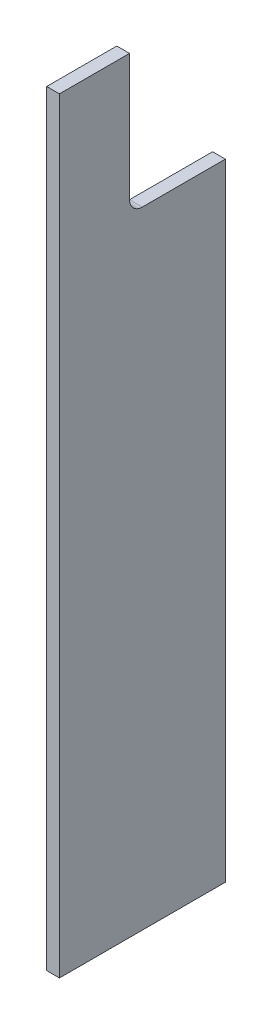
SolidWorks part; units mm, degrees
ref_plane "Plan de face" through (0, 0, 0) normal (0, 0, 1) x (1, 0, 0)
ref_plane "Plan de dessus" through (0, 0, 0) normal (0, 1, 0) x (1, 0, 0)
ref_plane "Plan de droite" through (0, 0, 0) normal (1, 0, 0) x (0, 0, -1)
sketch "Esquisse1" plane through (0, 0, 0) normal (0, 0, 1) x (1, 0, 0)
  line L0 (-91.2495, 0) -> (-222.1354, 0) construction
  line L1 (-155.642, 600) -> (-165.642, 600)
  line L2 (-155.642, 600) -> (-155.642, 0)
  line L3 (-155.642, 0) -> (-165.642, 0)
  line L4 (-165.642, 600) -> (-165.642, 0)
  dimension "D1" = 10
extrude "Boss.-Extru.1" add sketch "Esquisse1" along normal up to surface (129.974 mm away)
sketch "Esquisse2" plane through (-155.642, 0, 0) normal (1, 0, 0) x (0, 0, -1)
  line L0 (0, 0) -> (0, 600) construction
  line L1 (0, 600) -> (-75.046, 600)
  line L2 (0, 600) -> (0, 490.7165)
  line L3 (0, 490.7165) -> (-65.046, 490.7165)
  line L4 (-75.046, 600) -> (-75.046, 500.7165)
  line L5 (-129.974, 600) -> (0, 600) construction
  arc A0 (-65.046, 490.7165) -> (-75.046, 500.7165) centre (-65.046, 500.7165) cw
  dimension "D1" = 10
extrude "Enlèv. mat.-Extru.1" cut sketch "Esquisse2" against normal blind 10
sketch "Esquisse3" plane through (-165.642, 0, 0) normal (-1, 0, 0) x (0, 0, 1)
  line L2 (107.8435, 493.8958) -> (83.6926, 493.8958)
  line L3 (107.8435, 493.8958) -> (107.8435, 105.0056)
  line L4 (107.8435, 105.0056) -> (83.6926, 105.0056)
  line L5 (83.6926, 493.8958) -> (83.6926, 105.0056)
extrude "Enlèv. mat.-Extru.2" cut sketch "Esquisse3" against normal blind 5
